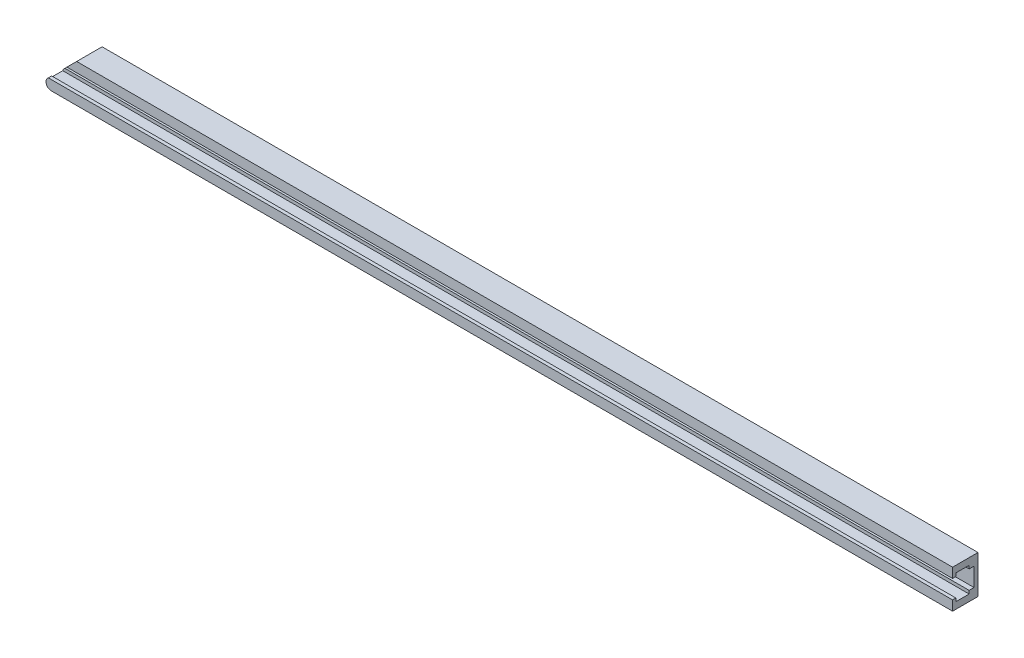
SolidWorks part; units mm, degrees
ref_plane "Front" through (0, 0, 0) normal (0, 0, 1) x (1, 0, 0)
ref_plane "Top" through (0, 0, 0) normal (0, 1, 0) x (1, 0, 0)
ref_plane "Right" through (0, 0, 0) normal (1, 0, 0) x (0, 0, -1)
sketch "Sketch1" plane through (0, 0, 0) normal (1, 0, 0) x (0, 0, -1)
  line L1 (0, 9.144) -> (-12.192, 9.144)
  line L2 (0, 9.144) -> (0, -9.144)
  line L3 (0, -9.144) -> (-12.192, -9.144)
  line L4 (-12.192, 9.144) -> (-12.192, -9.144)
  point P4 (0, 0)
  dimension "D1" = 18.288
  dimension "D2" = 12.192
sketch "Sketch2" plane through (0, 0, 0) normal (1, 0, 0) x (0, 0, -1)
  line L0 (0, 9.144) -> (-12.192, 9.144)
  line L1 (-12.192, 9.144) -> (-12.192, 4.445)
  line L2 (-12.192, 9.144) -> (-12.192, -9.144) construction
  line L3 (-12.192, 4.445) -> (-10.6045, 4.445)
  line L4 (-10.6045, 4.445) -> (-10.6045, 5.969)
  line L5 (-10.6045, 5.969) -> (-4.2545, 5.969)
  line L6 (-4.2545, 5.969) -> (-4.2545, 4.445)
  line L7 (-4.2545, 4.445) -> (-1.905, 4.445)
  line L8 (-1.905, 4.445) -> (-1.905, -4.445)
  line L9 (-1.905, -4.445) -> (-4.2545, -4.445)
  line L10 (-4.2545, -4.445) -> (-4.2545, -5.969)
  line L11 (-4.2545, -5.969) -> (-10.6045, -5.969)
  line L12 (-10.6045, -5.969) -> (-10.6045, -4.445)
  line L13 (-10.6045, -4.445) -> (-12.192, -4.445)
  line L14 (-12.192, -4.445) -> (-12.192, -9.144)
  line L15 (-12.192, -9.144) -> (0, -9.144)
  line L16 (0, -9.144) -> (0, 9.144)
  line L17 (0, 0) -> (-19.0377, 0) construction
  point P25 (-1.905, 0)
  dimension "D1" = 1.905
  dimension "D2" = 8.89
  dimension "D3" = 3.175
  dimension "D4" = 6.35
  dimension "D5" = 8.89
  dimension "D6" = 1.5875
extrude "Boss-Extrude1" add sketch "Sketch2" along normal mid plane 457.2
sketch "Sketch3" plane through (0, 0, 1.905) normal (0, 0, 1) x (1, 0, 0)
  line L0 (0, 0) -> (38.1, 0) construction
  line L1 (0, 0) -> (0, 27.0833) construction
  circle A0 centre (38.1, 0) radius 2.413
  dimension "D2" = 4.826
  dimension "D1" = 76.2
extrude "Cut-Extrude1" cut sketch "Sketch3" against normal up to surface (1.905 mm away) up to face at (0, 0, 0)
pattern_linear "LPattern1" count 3 spacing 76.2 along (1, 0, 0) of "Cut-Extrude1"
other "SurfaceCut1"
mirror "Mirror1" about plane through (0, 0, 0) normal (1, 0, 0) of bodies 112
sketch "Sketch4" plane through (0, 0, 12.192) normal (0, 0, 1) x (1, 0, 0)
  line L0 (228.6, -9.144) -> (204.1995, -33.5445) construction
  line L1 (228.6, -9.144) -> (193.128, -9.144) construction
  line L2 (218.1669, 9.144) -> (228.6, 9.144)
  line L3 (199.8789, -9.144) -> (218.1669, 9.144)
  line L4 (228.6, 9.144) -> (-228.6, 9.144) construction
  line L5 (228.6, 9.144) -> (228.6, -9.144)
  line L6 (228.6, -9.144) -> (199.8789, -9.144)
  line L7 (-209.55, -9.144) -> (-191.262, 9.144)
  line L8 (-209.55, -9.144) -> (-228.6, -9.144)
  line L9 (-228.6, -9.144) -> (-228.6, 9.144)
  line L10 (-228.6, 9.144) -> (-191.262, 9.144)
  dimension "D1" = 45
  dimension "D2" = 45
  dimension "D3" = 45
  dimension "D4" = 19.05
extrude "Cut-Extrude3" cut sketch "Sketch4" against normal through all contours L7 L10 L9 L8
fillet "Fillet1" radius 2.54 1 edges at (-209.55, -9.144, 6.096)
